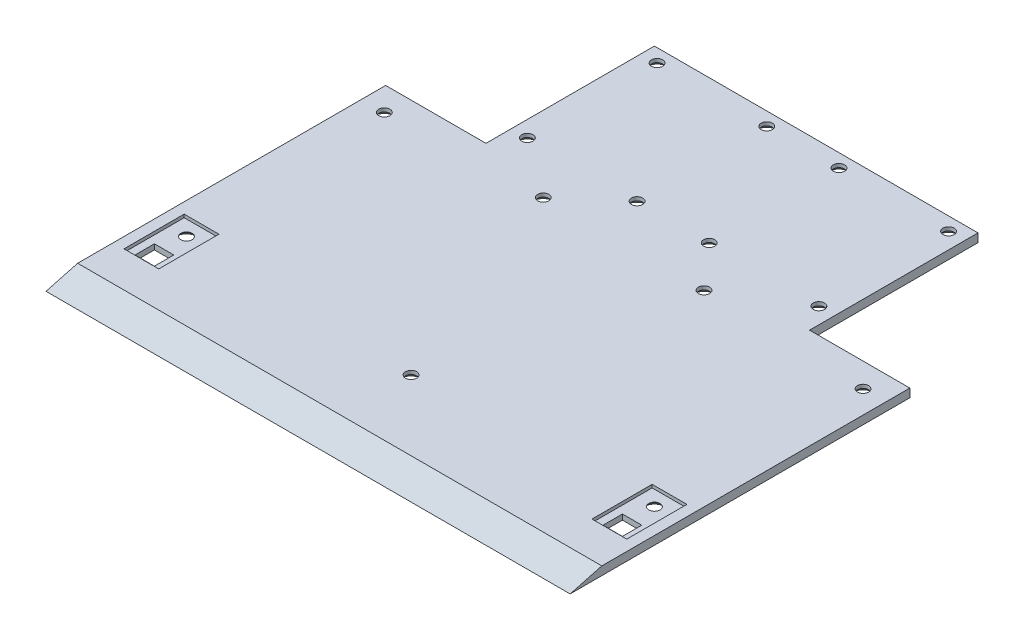
SolidWorks part; units mm, degrees
ref_plane "Alzado" through (0, 0, 0) normal (0, 0, 1) x (1, 0, 0)
ref_plane "Planta" through (0, 0, 0) normal (0, 1, 0) x (1, 0, 0)
ref_plane "Vista lateral" through (0, 0, 0) normal (1, 0, 0) x (0, 0, -1)
sketch "Croquis1" plane through (0, 0, 0) normal (1, 0, 0) x (0, 0, -1)
  line L0 (0, 0) -> (190, 0)
  line L1 (190, 0) -> (190, 3.17)
  line L2 (190, 3.17) -> (11.8306, 3.17)
  line L3 (0, 0) -> (11.8306, 3.17)
  dimension "D1" = 190
  dimension "D2" = 3.17
  dimension "D3" = 165
extrude "Saliente-Extruir1" add sketch "Croquis1" along normal blind 196
sketch "Croquis2" plane through (0, 0, 0) normal (0, -1, 0) x (-1, 0, 0)
  line L0 (0, 190) -> (0, 11.8306) construction
  line L1 (0, 127.0101) -> (-37.5, 127.0101)
  line L2 (0, 127.0101) -> (0, 190)
  line L3 (0, 190) -> (-37.5, 190)
  line L4 (-37.5, 127.0101) -> (-37.5, 190)
  line L5 (0, 127.0101) -> (-37.5, 190) construction
  line L6 (0, 190) -> (-37.5, 127.0101) construction
  line L7 (-196, 127.0101) -> (0, 127.0101) construction
  line L8 (-196, 190) -> (0, 190) construction
  line L9 (-37.5, 131.5) -> (-37.5, 190) construction
  point P4 (-18.75, 158.5051)
extrude "Cortar-Extruir1" cut sketch "Croquis2" against normal up to next
ref_plane "Plano1" through (98, 0, 0) normal (-1, 0, 0) x (0, 0, 1)
mirror "Simetría1" about plane through (98, 0, 0) normal (-1, 0, 0) of "Cortar-Extruir1"
sketch "Croquis3" plane through (0, 3.17, 0) normal (0, 1, 0) x (1, 0, 0)
  line L0 (196, 0) -> (0, 0) construction
  line L1 (4, 47.66) -> (17, 47.66)
  line L2 (4, 47.66) -> (4, 25.16)
  line L3 (4, 25.16) -> (17, 25.16)
  line L4 (17, 47.66) -> (17, 25.16)
  line L5 (4, 47.66) -> (17, 25.16) construction
  line L6 (4, 25.16) -> (17, 47.66) construction
  line L7 (0, 127.0101) -> (0, 11.8306) construction
  point P4 (10.5, 36.41)
  dimension "D1" = 25.16
  dimension "D2" = 22.5
  dimension "D3" = 13
  dimension "D4" = 4
extrude "Cortar-Extruir2" cut sketch "Croquis3" against normal blind 1.17
sketch "Croquis4" plane through (0, 2, 0) normal (0, 1, 0) x (1, 0, 0)
  line L0 (10.5, 25.16) -> (10.5, 26.41) construction
  line L1 (4, 25.16) -> (17, 25.16) construction
  line L2 (4, 26.41) -> (17, 26.41) construction
  line L3 (4, 47.66) -> (4, 25.16) construction
  line L4 (17, 25.16) -> (17, 47.66) construction
  line L5 (10.5, 26.41) -> (10.5, 33.66) construction
  line L6 (10.5, 30.035) -> (6.875, 30.035) construction
  line L7 (10.5, 30.035) -> (14.125, 30.035) construction
  line L8 (6.875, 30.035) -> (6.875, 26.41) construction
  line L9 (14.125, 30.035) -> (14.125, 33.66) construction
  dimension "D1" = 1.25
  dimension "D2" = 7.25
  dimension "D3" = 3.625
  dimension "D4" = 3.625
sketch "Croquis5" plane through (0, 2, 0) normal (0, 1, 0) x (1, 0, 0)
  line L1 (6.875, 26.41) -> (14.125, 26.41)
  line L2 (6.875, 26.41) -> (6.875, 33.66)
  line L3 (6.875, 33.66) -> (14.125, 33.66)
  line L4 (14.125, 26.41) -> (14.125, 33.66)
  line L5 (6.875, 26.41) -> (14.125, 33.66) construction
  line L6 (6.875, 33.66) -> (14.125, 26.41) construction
  point P4 (10.5, 30.035)
extrude "Cortar-Extruir3" cut sketch "Croquis5" against normal up to next
sketch "Croquis6" plane through (0, 2, 0) normal (0, 1, 0) x (1, 0, 0)
  line L0 (10.5, 47.66) -> (10.5, 46.41) construction
  line L1 (17, 47.66) -> (4, 47.66) construction
  line L2 (10.5, 46.41) -> (17, 46.41) construction
  line L3 (17, 25.16) -> (17, 47.66) construction
  line L4 (17, 46.41) -> (4, 46.41) construction
  line L5 (4, 47.66) -> (4, 25.16) construction
  circle A0 centre (10.5, 42.01) radius 1.6
  dimension "D2" = 3.2
  dimension "D1" = 1.25
  dimension "D3" = 4.4
extrude "Cortar-Extruir4" cut sketch "Croquis6" against normal up to next
mirror "Simetría2" about plane through (98, 0, 0) normal (-1, 0, 0) of "Cortar-Extruir2", "Cortar-Extruir4", "Cortar-Extruir3"
sketch "Sketch1" plane through (0, 3.17, 0) normal (0, 1, 0) x (1, 0, 0)
  circle A0 centre (8.5, 118.0101) radius 1.585
  circle A1 centre (187.5, 118.0101) radius 1.585
extrude "Cut-Extrude1" cut sketch "Sketch1" against normal up to next
sketch "Sketch2" plane through (0, 3.17, 0) normal (0, 1, 0) x (1, 0, 0)
  circle A0 centre (98.5, 38.0101) radius 1.585
extrude "Cut-Extrude2" cut sketch "Sketch2" against normal up to next
sketch "Sketch3" plane through (0, 3.17, 0) normal (0, 1, 0) x (1, 0, 0)
  circle A0 centre (43.5, 185) radius 1.5799
  circle A1 centre (84.5, 185) radius 1.585
  circle A2 centre (152.5, 185) radius 1.585
  circle A3 centre (111.5, 185) radius 1.585
  circle A4 centre (111.5, 136.5) radius 1.585
  circle A5 centre (152.5, 136.5) radius 1.585
  circle A6 centre (84.5, 136.5) radius 1.585
  circle A7 centre (43.5, 136.5) radius 1.585
extrude "Cut-Extrude3" cut sketch "Sketch3" against normal up to next
sketch "Sketch4" plane through (0, 3.17, 0) normal (0, 1, 0) x (1, 0, 0)
  circle A0 centre (65.7764, 120.1669) radius 1.6
  circle A1 centre (125.8764, 120.1669) radius 1.6
extrude "Cut-Extrude4" cut sketch "Sketch4" against normal blind 4.9
hole_wizard "Avellanado para tornillo con cabeza avellanada en cruz de M3.51" positions "3DSketch1" profile "Sketch5" countersink size "M3.5" standard "AS"
sketch3d "3DSketch1"
  line L0 (187.5, 0, -118.0101) -> (187.5, 3.17, -118.0101) construction
  line L1 (152.5, 0, -136.5) -> (152.5, 3.17, -136.5) construction
  line L2 (125.8764, 0, -120.1669) -> (125.8764, 3.17, -120.1669) construction
  line L3 (111.5, 0, -136.5) -> (111.5, 3.17, -136.5) construction
  line L4 (84.5, 0, -136.5) -> (84.5, 3.17, -136.5) construction
  line L5 (65.7764, 0, -120.1669) -> (65.7764, 3.17, -120.1669) construction
  line L6 (43.5, 0, -136.5) -> (43.5, 3.17, -136.5) construction
  line L7 (8.5, 0, -118.0101) -> (8.5, 3.17, -118.0101) construction
  line L8 (43.5, 0, -185) -> (43.5, 3.17, -185) construction
  line L9 (84.5, 0, -185) -> (84.5, 3.17, -185) construction
  line L10 (111.5, 0, -185) -> (111.5, 3.17, -185) construction
  line L11 (152.5, 0, -185) -> (152.5, 3.17, -185) construction
  line L12 (10.5, 0, -42.01) -> (10.5, 2, -42.01) construction
  line L13 (98.5, 0, -38.0101) -> (98.5, 3.17, -38.0101) construction
  line L14 (185.5, 0, -42.01) -> (185.5, 2, -42.01) construction
  point P0 (187.5, 0, -118.0101)
  point P4 (152.5, 0, -136.5)
  point P8 (125.8764, 0, -120.1669)
  point P12 (111.5, 0, -136.5)
  point P16 (84.5, 0, -136.5)
  point P20 (65.7764, 0, -120.1669)
  point P24 (43.5, 0, -136.5)
  point P28 (8.5, 0, -118.0101)
  point P32 (43.5, 0, -185)
  point P36 (84.5, 0, -185)
  point P40 (111.5, 0, -185)
  point P44 (152.5, 0, -185)
  point P48 (10.5, 0, -42.01)
  point P52 (98.5, 0, -38.0101)
  point P56 (185.5, 0, -42.01)
sketch "Sketch5" plane through (187.5, 0, -118.0101) normal (1, 0, 0) x (0, 0, -1)
  line L0 (0, 0) -> (0, 11.2618)
  line L1 (0, 11.2618) -> (2.1, 10)
  line L2 (2.1, 10) -> (2.1, 1.8348)
  line L3 (2.1, 1.8348) -> (4, 0)
  line L5 (4, 0) -> (0, 0)
  line L6 (-2.1, 1.8348) -> (-4, 0) construction
  line L10 (0, 11.2618) -> (-2.1, 10) construction
  line L11 (0, -6.35) -> (0, 107.95) construction
  dimension "Diámetro de taladro" = 4.2
  dimension "Profundidad de taladro" = 10
  dimension "Ángulo de avellanado cercano" = 8
  dimension "Ángulo de avellanado lejano" = 92
  dimension "Ángulo de perforador" = 118
